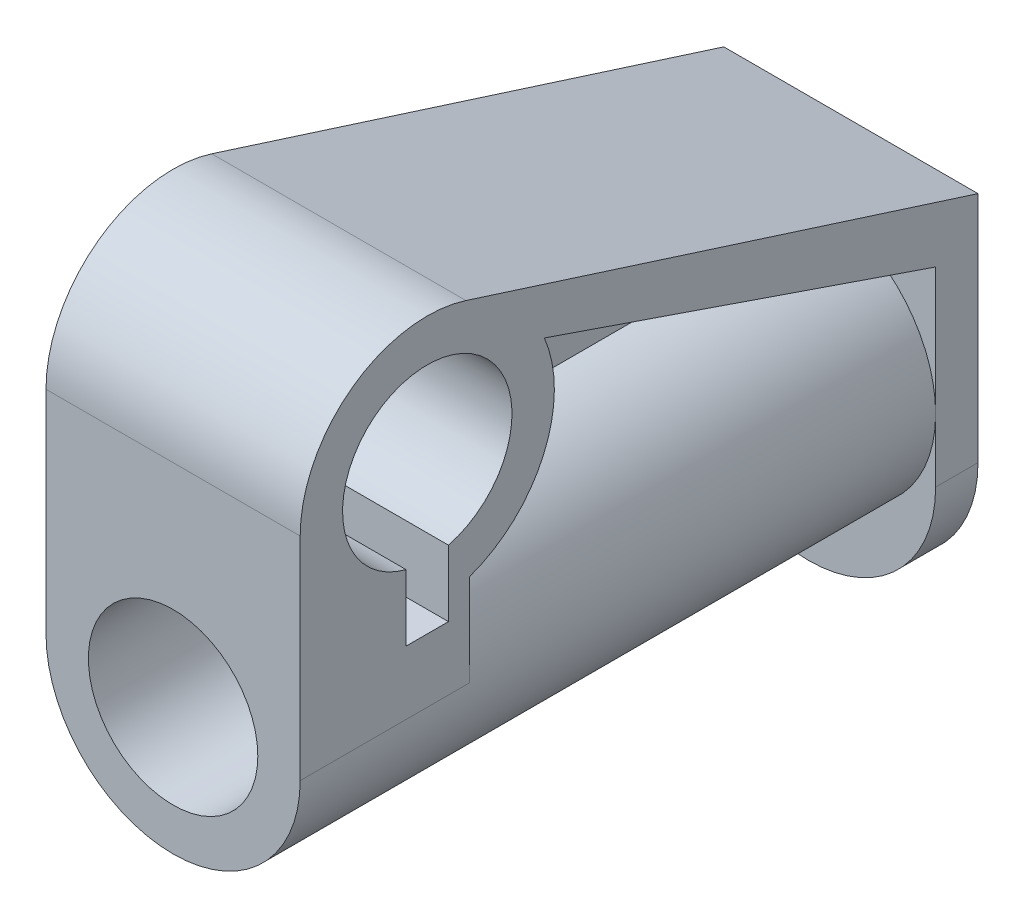
SolidWorks part; units mm, degrees
ref_plane "Front Plane" through (0, 0, 0) normal (0, 0, 1) x (1, 0, 0)
ref_plane "Top Plane" through (0, 0, 0) normal (0, 1, 0) x (1, 0, 0)
ref_plane "Right Plane" through (0, 0, 0) normal (1, 0, 0) x (0, 0, -1)
sketch "Sketch1" plane through (0, 0, 0) normal (0, 0, 1) x (1, 0, 0)
  line L0 (0, 0) -> (0, -7.5)
  line L1 (-15, -7.5) -> (-15, 0)
  line L2 (15, 0) -> (15, -7.5)
  circle A0 centre (0, 0) radius 15
  circle A1 centre (0, 0) radius 10
  arc A2 (-15, -7.5) -> (15, -7.5) centre (0, -7.5) ccw
extrude "Boss-Extrude1" add sketch "Sketch1" along normal blind 80 contours A0 A1 region at (0, 14.5757, 0)
extrude "Boss-Extrude2" add sketch "Sketch1<3>" along normal blind 5 contours L1 A2 L2 A0 region at (0, -15.531, 0)
sketch "Sketch1<3>" plane through (0, 0, 0) normal (0, 0, 1) x (1, 0, 0) same geometry as "Sketch1"
sketch "Sketch2" plane through (0, 0, 0) normal (1, 0, 0) x (0, 0, -1)
  line L0 (-80, 25) -> (-80, 0)
  line L1 (-5, 15) -> (-5, 10)
  line L2 (-5, 15) -> (-5, 0)
  line L3 (-67.5, 15.3175) -> (-67.5, 7.5)
  line L4 (-67.5, 7.5) -> (-62.5, 7.5)
  line L5 (-62.5, 7.5) -> (-62.5, 15.3175)
  line L6 (0, 0) -> (0, 15) construction
  line L7 (0, 15) -> (0, 20)
  line L8 (0, 20) -> (-60.4392, 39.2898)
  line L9 (-5, 10) -> (-60, 10)
  line L10 (-5, 15) -> (-51.1808, 30.8334)
  line L11 (-5, 0) -> (0, 0)
  line L12 (0, 0) -> (0, 15)
  line L13 (0, 15) -> (-0.2144, 15.2483)
  line L14 (-60, 10.8579) -> (-60, 0)
  line L15 (-80, 15) -> (-80, -15) construction
  line L16 (-80, 0) -> (-60, 0)
  arc A0 (-60.4392, 39.2898) -> (-80, 25) centre (-65, 25) ccw
  arc A1 (-60, 10.8579) -> (-51.1808, 30.8334) centre (-65, 25) ccw
  arc A2 (-62.5, 15.3175) -> (-67.5, 15.3175) centre (-65, 25) ccw
extrude "Boss-Extrude3" add sketch "Sketch2" along normal mid plane 30 contours L14 A1 L10 L2 L11 L12 L7 L8 A0 L0 L16 A2 L5 L4 L3 region at (0, 36.39, 73.3208)
extrude "Boss-Extrude21" add sketch "Sketch2<8>" along normal mid plane 5 contours A1 L14 L9 L1 L10 region at (0, 16.8978, 33.6997)
sketch "Sketch2<8>" plane through (0, 0, 0) normal (1, 0, 0) x (0, 0, -1) same geometry as "Sketch2"
extrude "Cut-Extrude1" cut sketch "Sketch2<9>" against normal mid plane 30 contours L5 A2 L3 L4 region at (0, 23.5211, 65)
sketch "Sketch2<9>" plane through (0, 0, 0) normal (1, 0, 0) x (0, 0, -1) same geometry as "Sketch2"
extrude "Cut-Extrude2" cut sketch "Sketch1<4>" along normal blind 80 contours A1 region at (-9.7172, 0, 0)
sketch "Sketch1<4>" plane through (0, 0, 0) normal (0, 0, 1) x (1, 0, 0) same geometry as "Sketch1"
